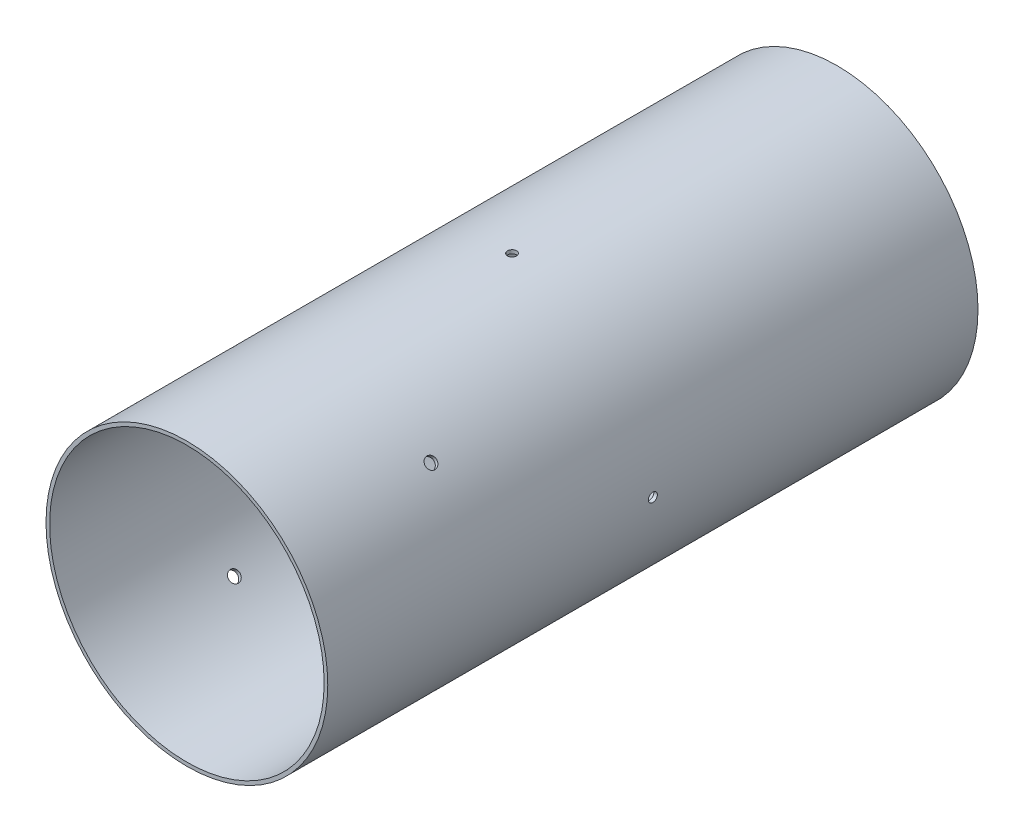
SolidWorks part; units mm, degrees
ref_plane "Front Plane" through (0, 0, 0) normal (0, 0, 1) x (1, 0, 0)
ref_plane "Top Plane" through (0, 0, 0) normal (0, 1, 0) x (1, 0, 0)
ref_plane "Right Plane" through (0, 0, 0) normal (1, 0, 0) x (0, 0, -1)
sketch "Sketch1" plane through (0, 0, 0) normal (0, 0, 1) x (1, 0, 0)
  circle A0 centre (0, 0) radius 49.53
  circle A1 centre (0, 0) radius 48.26
  dimension "D1" = 99.06
  dimension "D2" = 96.52
extrude "Boss-Extrude1" add sketch "Sketch1" along normal blind 228.6
extrude "Cut-Extrude1" cut sketch "Sketch2" against normal blind 12.7
sketch "Sketch2" plane through (-120.5803, -48.7382, -78.9954) normal (-0.7071, 0.7071, 0) x (0.7071, 0.7071, 0)
  circle A0 centre (119.7263, -256.7954) radius 1.9844
pattern_circular "CirPattern1" count 4 over 360 of "Cut-Extrude1"
extrude "Cut-Extrude2" cut sketch "Sketch3" against normal blind 25.4
sketch "Sketch3" plane through (-108.0218, -85.4992, -79.3332) normal (-0.866, 0.5, 0) x (0, 0, 1)
  circle A0 centre (196.8082, 128.0554) radius 2.3813
  circle A1 centre (190.4582, 128.0554) radius 2.3813
extrude "Cut-Extrude3" cut sketch "Sketch4" against normal blind 37.338
sketch "Sketch4" plane through (-33.6632, -130.5648, -80.7782) normal (1, 0, 0) x (0, 0, -1)
  circle A0 centre (-195.0782, 130.5648) radius 1.5875
  point P3 (-80.7782, 130.5648)
  point P4 (-195.0782, 181.3648)
pattern_circular "CirPattern2" count 4 over 360 about axis through (0, 0, 228.6) along (0, 0, -1) of "Cut-Extrude3" reverse direction yes
extrude "Cut-Extrude4" cut sketch "Sketch5" against normal blind 25.4
sketch "Sketch5" plane through (-120.5803, -48.7382, -78.9954) normal (-0.7071, 0.7071, 0) x (0.7071, 0.7071, 0)
  line L0 (68.9263, -129.7954) -> (170.5263, -129.7954) construction
  circle A0 centre (119.7263, -129.7954) radius 1.0922
  point P8 (0, 0)
  point P9 (0, 0)
pattern_circular "CirPattern3" count 2 over 360 of "Cut-Extrude4"
